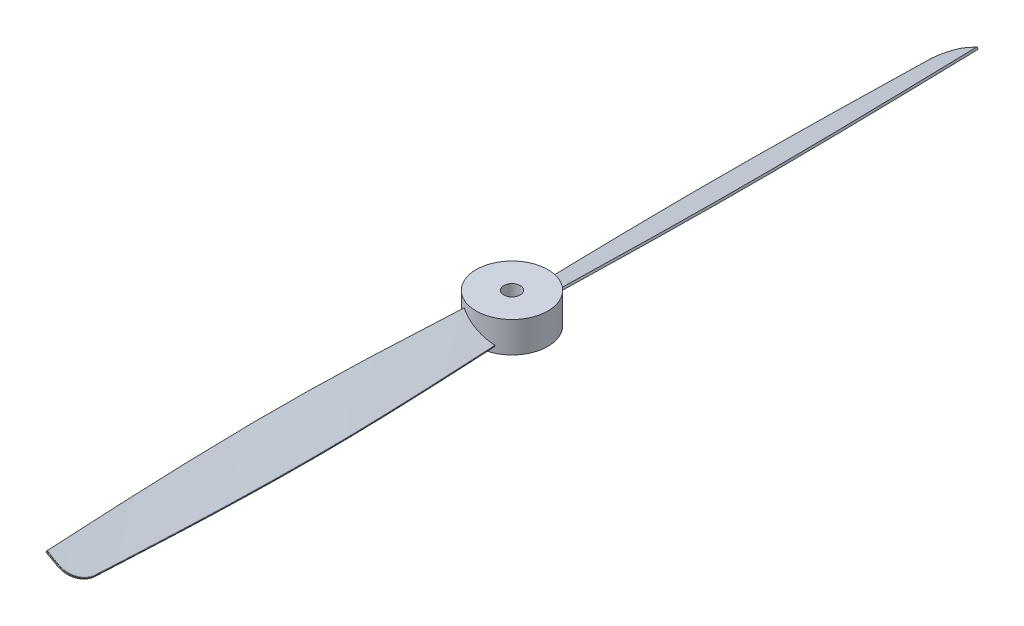
SolidWorks part; units mm, degrees
ref_plane "Front Plane" through (0, 0, 0) normal (0, 0, 1) x (1, 0, 0)
ref_plane "Top Plane" through (0, 0, 0) normal (0, 1, 0) x (1, 0, 0)
ref_plane "Right Plane" through (0, 0, 0) normal (1, 0, 0) x (0, 0, -1)
sketch "Sketch1" plane through (0, 0, 0) normal (0, 1, 0) x (1, 0, 0)
  circle A0 centre (0, 0) radius 17.5
  dimension "D1" = 35
extrude "Boss-Extrude1" add sketch "Sketch1" along normal mid plane 15
sketch "Sketch2" plane through (0, 0, 0) normal (0, 0, 1) x (1, 0, 0)
  line L0 (0, 12.3252) -> (0, -12.0696) construction
  line L1 (-7.4687, 3.0363) -> (-6.98, 3.9088)
  line L2 (-7.4687, 3.0363) -> (6.4914, -4.7813)
  line L3 (-6.98, 3.9088) -> (6.98, -3.9088)
  line L4 (6.4914, -4.7813) -> (6.98, -3.9088)
  dimension "D1" = 16
  dimension "D2" = 1
ref_plane "Plane1" through (0, 0, 100) normal (0, 0, 1) x (1, 0, 0)
sketch "Sketch3" plane through (0, 0, 100) normal (0, 0, 1) x (1, 0, 0)
  line L0 (-9.8041, 4.988) -> (-10.2575, 4.0968)
  line L1 (-9.8041, 4.988) -> (9.8041, -4.988)
  line L2 (-10.2575, 4.0968) -> (9.3506, -5.8793)
  line L3 (9.8041, -4.988) -> (9.3506, -5.8793)
  dimension "D1" = 22
  dimension "D2" = 1
ref_plane "Plane2" through (0, 0, 220) normal (0, 0, 1) x (1, 0, 0)
sketch "Sketch4" plane through (0, 0, 220) normal (0, 0, 1) x (1, 0, 0)
  line L0 (6.4914, -4.7813) -> (6.98, -3.9088) construction
  line L1 (-6.98, 3.9088) -> (6.98, -3.9088) construction
  line L2 (-7.4687, 3.0363) -> (6.4914, -4.7813) construction
  line L3 (-7.4687, 3.0363) -> (-6.98, 3.9088) construction
  line L4 (6.4914, -4.7813) -> (6.98, -3.9088)
  line L5 (-6.98, 3.9088) -> (6.98, -3.9088)
  line L6 (-7.4687, 3.0363) -> (6.4914, -4.7813)
  line L7 (-7.4687, 3.0363) -> (-6.98, 3.9088)
loft "Loft1" add profiles "Sketch2", "Sketch3", "Sketch4" connector at (6.98, -3.9088, 0) connector at (9.8041, -4.988, 100) connector at (6.98, -3.9088, 220)
fillet "Fillet1" radius 10 1 edges
fillet "Fillet2" radius 0.2 6 edges at (4.0495, -2.2593, 217.8087) (4.7074, -3.7654, 216.5552)
pattern_circular "CirPattern1" count 2 over 360 about axis through (0, 7.5, 0) along (0, 1, 0) of "Loft1", "Fillet1", "Fillet2"
sketch "Sketch5" plane through (0, -7.5, 0) normal (0, -1, 0) x (1, 0, 0)
  circle A0 centre (0, 0) radius 4
  dimension "D1" = 8
extrude "Cut-Extrude1" cut sketch "Sketch5" against normal through all
